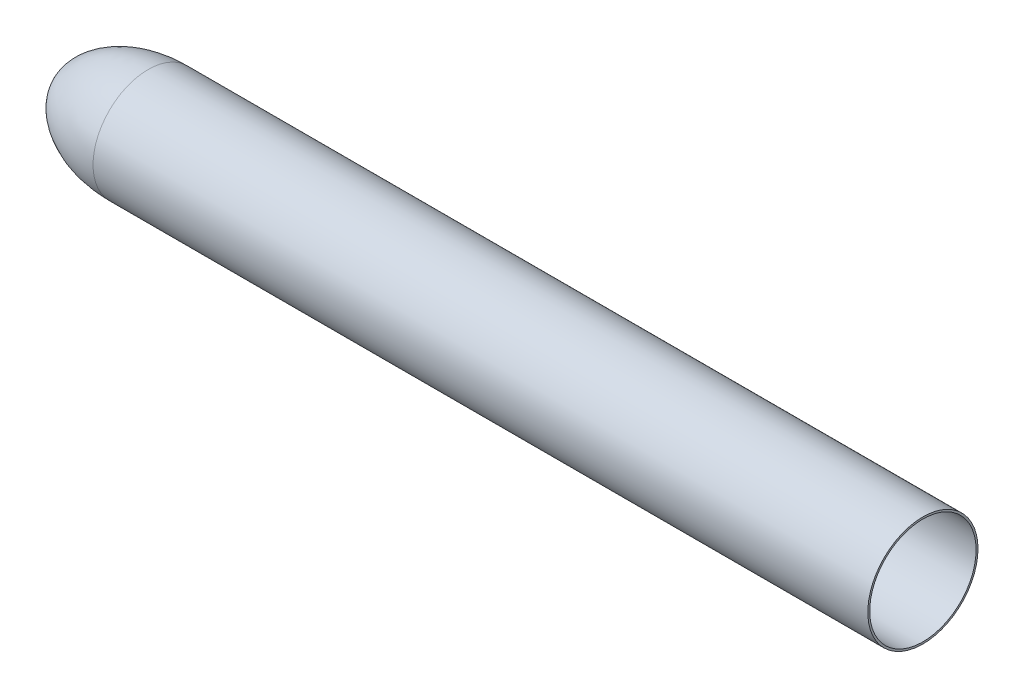
SolidWorks part; units mm, degrees
material "7075-T6 (SN)"
ref_plane "Front Plane" through (0, 0, 0) normal (0, 0, 1) x (1, 0, 0)
ref_plane "Top Plane" through (0, 0, 0) normal (0, 1, 0) x (1, 0, 0)
ref_plane "Right Plane" through (0, 0, 0) normal (1, 0, 0) x (0, 0, -1)
sketch "Sketch1" plane through (0, 0, 0) normal (1, 0, 0) x (0, 0, -1)
  circle A0 centre (0, 0) radius 1600
  dimension "D1" = 3200
extrude "Body Extrude" add sketch "Sketch1" against normal blind 22500 contours A0
dome "Rocket Tip Dome" faces to dome 1 distance 2500 reverse direction no elliptical dome yes face at (-22500, 0, -1600) parameters "D1"=2500
shell "Shell = 55mm" thickness 55 removed face at (0, 0, -1600)
ref_plane "Plane1" through (-2500, 0, 0) normal (1, 0, 0) x (0, 0, -1)
sketch "Sketch2" plane through (-2500, 0, 0) normal (1, 0, 0) x (0, 0, -1)
  circle A0 centre (0, 0) radius 1400
  circle A3 centre (0, 0) radius 1545
  circle A4 centre (0, 0) radius 1545
  dimension "D1" = 2800
  dimension "D2" = 0
extrude "Engine Mount Extrude" add sketch "Sketch2" against normal blind 300
ref_plane "Plane2" through (-2425, 0, 0) normal (1, 0, 0) x (0, 0, -1)
sketch "Sketch3" plane through (-2425, 0, 0) normal (1, 0, 0) x (0, 0, -1)
  line L0 (0, -1895.8803) -> (0, 1895.8803) construction
  line L1 (-2104.8943, 0) -> (2104.8943, 0) construction
  line L2 (755, 1307.6984) -> (772.5, 1338.0092)
  line L3 (-755, 1307.6984) -> (-772.5, 1338.0092)
  line L4 (-755, -1307.6984) -> (-772.5, -1338.0092)
  line L5 (755, -1307.6984) -> (772.5, -1338.0092)
  arc A1 (772.5, 1338.0092) -> (-772.5, 1338.0092) centre (0, 0) ccw
  arc A2 (755, 1307.6984) -> (-755, 1307.6984) centre (0, 0) ccw
  arc A4 (755, -1307.6984) -> (-755, -1307.6984) centre (0, 0) cw
  arc A5 (772.5, -1338.0092) -> (-772.5, -1338.0092) centre (0, 0) cw
  point P6 (0, 0)
  point P10 (0, 0)
  dimension "D2" = 30
  dimension "D3" = 35
extrude "Slots" add sketch "Sketch3" along normal blind 75
ref_plane "Plane3" through (0, 0, 1600) normal (0, 0, 1) x (1, 0, 0)
sketch "Sketch13" plane through (0, 0, 0) normal (0, 0, 1) x (1, 0, 0)
  line L0 (-2425, -1545) -> (-2404.7927, -1510)
  line L1 (-2425, -1510) -> (-2404.7927, -1510)
  line L2 (-2425, -1510) -> (-2425, -1545)
  line L4 (-2350, -1510) -> (-2350, -1545)
  line L5 (-2387.5, -1555.6947) -> (-2387.5, -1503.7634) construction
  line L6 (-2350, -1545) -> (-2370.2073, -1510)
  line L7 (-2370.2073, -1510) -> (-2350, -1510)
  line L8 (0, 0) -> (-477.0108, 0) construction
  dimension "D1" = 75
  dimension "D2" = 35
  dimension "D3" = 2350
revolve "Dovetail Cut Slots" cut sketch "Sketch13" angle 60 mid plane about L8
